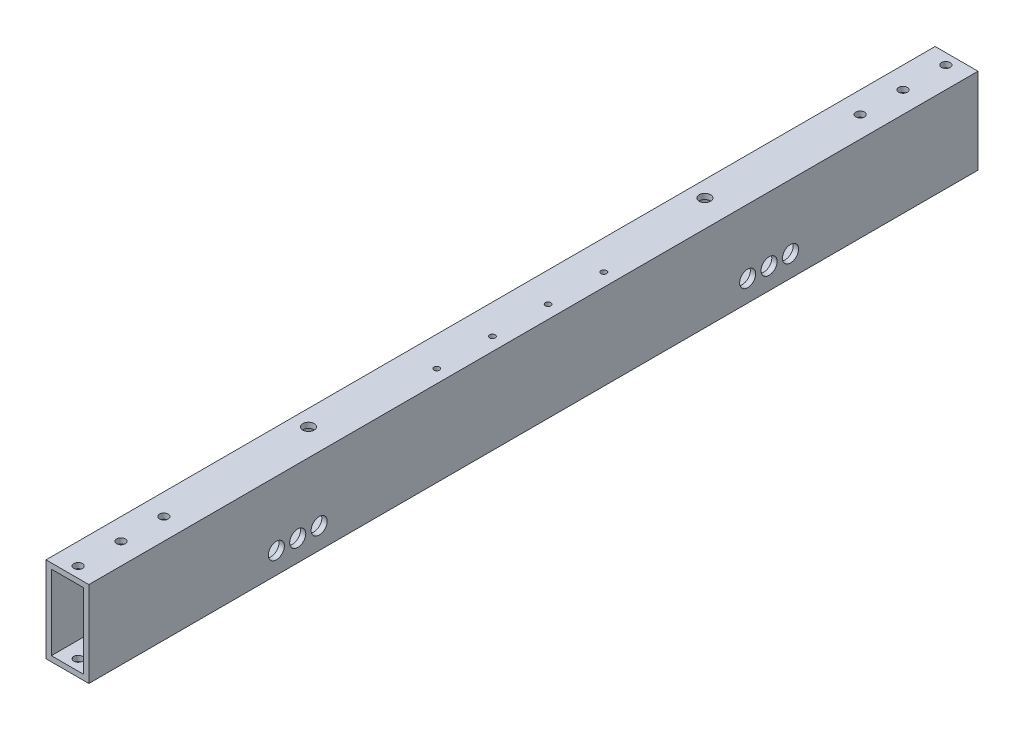
SolidWorks part; units mm, degrees
material "6061-T6 (SS)"
ref_plane "Front" through (0, 0, 0) normal (0, 0, 1) x (1, 0, 0)
ref_plane "Top" through (0, 0, 0) normal (0, 1, 0) x (1, 0, 0)
ref_plane "Right" through (0, 0, 0) normal (1, 0, 0) x (0, 0, -1)
sketch "Sketch1" plane through (0, 0, 0) normal (0, 0, 1) x (1, 0, 0)
  line L1 (-12.7, -25.4) -> (12.7, -25.4)
  line L2 (-12.7, -25.4) -> (-12.7, 25.4)
  line L3 (-12.7, 25.4) -> (12.7, 25.4)
  line L4 (12.7, -25.4) -> (12.7, 25.4)
  line L5 (-12.7, -25.4) -> (12.7, 25.4) construction
  line L6 (-12.7, 25.4) -> (12.7, -25.4) construction
  point P0 (0, 0)
  dimension "D1" = 25.4
  dimension "D2" = 50.8
extrude "Extrude-Thin1" add sketch "Sketch1" along normal blind 527.05 thin thin type one direction reverse wall 3.175
hole_wizard "#10 Clearance Hole1" positions "Sketch2" profile "Sketch3" hole size "#10" standard "ANSI Inch" end condition through all
sketch "Sketch2" plane through (0, 25.4, 0) normal (0, 1, 0) x (1, 0, 0)
  line L0 (12.7, -527.05) -> (-12.7, -527.05) construction
  line L1 (-12.7, -527.05) -> (-12.7, 0) construction
  point P0 (0, -520.7)
  point P2 (0, -495.3)
  point P4 (0, -469.9)
  point P13 (0, -6.35)
  point P15 (0, -31.75)
  point P17 (0, -57.15)
  dimension "D1" = 6.35
  dimension "D2" = 25.4
  dimension "D3" = 25.4
  dimension "D4" = 12.7
  dimension "D5" = 6.35
  dimension "D6" = 25.4
  dimension "D7" = 25.4
sketch "Sketch3" plane through (0, 25.4, 520.7) normal (1, 0, 0) x (0, 0, 1)
  line L0 (0, 0) -> (0, 50.8)
  line L1 (0, 50.8) -> (2.5527, 50.8)
  line L2 (2.5527, 50.8) -> (2.5527, 0)
  line L5 (2.5527, 0) -> (0, 0)
  line L11 (0, -6.35) -> (0, 107.95) construction
  dimension "Thru Hole Dia." = 5.1054
  dimension "Thru Hole Depth" = 50.8
sketch "Sketch8" plane through (0, -25.4, 0) normal (0, -1, 0) x (-1, 0, 0)
  point P0 (3.175, -451.358)
  point P3 (-3.175, -425.958)
  point P6 (3.175, -400.558)
  point P9 (-3.175, -375.158)
  point P12 (3.175, -349.758)
  point P19 (3.175, -298.958)
  point P26 (3.175, -248.158)
  point P29 (-3.175, -222.758)
  point P32 (3.175, -197.358)
  point P35 (-3.175, -171.958)
  point P38 (3.175, -146.558)
  point P41 (-3.175, -121.158)
  point P48 (-3.175, -70.358)
  point P55 (-3.175, -324.358)
  point P58 (-3.175, -273.558)
  point P61 (3.175, -95.758)
hole_wizard "1/8 (0.13) Diameter Hole1" positions "Sketch8" profile "Sketch7" hole size "1/8" standard "ANSI Inch" end condition up to next
sketch "Sketch7" plane through (-3.175, -25.4, 451.358) normal (1, 0, 0) x (0, 0, -1)
  line L0 (0, 0) -> (0, 3.175)
  line L1 (0, 3.175) -> (1.651, 3.175)
  line L2 (1.651, 3.175) -> (1.651, 0)
  line L5 (1.651, 0) -> (0, 0)
  line L11 (0, -6.35) -> (0, 107.95) construction
  dimension "Thru Hole Dia." = 3.302
  dimension "Thru Hole Depth" = 3.175
sketch "Sketch11" plane through (0, 25.4, 0) normal (0, 1, 0) x (1, 0, 0)
  point P0 (4.9213, -313.055)
  point P3 (4.9213, -280.035)
  point P6 (4.9213, -247.015)
  point P9 (4.9213, -213.995)
hole_wizard "1/8 (0.13) Diameter Hole2" positions "Sketch11" profile "Sketch10" hole size "1/8" standard "ANSI Inch" end condition up to next
sketch "Sketch10" plane through (4.9213, 25.4, 313.055) normal (1, 0, 0) x (0, 0, 1)
  line L0 (0, 0) -> (0, 3.175)
  line L1 (0, 3.175) -> (1.651, 3.175)
  line L2 (1.651, 3.175) -> (1.651, 0)
  line L5 (1.651, 0) -> (0, 0)
  line L11 (0, -6.35) -> (0, 107.95) construction
  dimension "Thru Hole Dia." = 3.302
  dimension "Thru Hole Depth" = 3.175
sketch "Sketch14" plane through (0, 25.4, 0) normal (0, 1, 0) x (1, 0, 0)
  line L0 (12.7, 0) -> (-12.7, 0) construction
  line L1 (12.7, -527.05) -> (-12.7, -527.05) construction
  line L2 (-12.7, -527.05) -> (-12.7, 0) construction
  point P0 (-3.175, -146.05)
  point P2 (-3.175, -381)
  dimension "D1" = 146.05
  dimension "D2" = 146.05
  dimension "D3" = 9.525
hole_wizard "1/4 Clearance Hole1" positions "Sketch14" profile "Sketch13" hole size "1/4" standard "ANSI Inch"
sketch "Sketch13" plane through (-3.175, 25.4, 146.05) normal (1, 0, 0) x (0, 0, 1)
  line L0 (0, 0) -> (0, 12.7486)
  line L1 (0, 12.7486) -> (3.3782, 10.7188)
  line L2 (3.3782, 10.7188) -> (3.3782, 0)
  line L5 (3.3782, 0) -> (0, 0)
  line L10 (0, 12.7486) -> (-3.3782, 10.7188) construction
  line L11 (0, -6.35) -> (0, 107.95) construction
  dimension "Hole Dia." = 6.7564
  dimension "Hole Depth" = 10.7188
  dimension "Drill Angle" = 118
sketch "Sketch17" plane through (12.7, 0, 0) normal (1, 0, 0) x (0, 0, -1)
  point P38 (-111.125, -12.7)
  point P41 (-123.825, -12.7)
  point P44 (-136.525, -12.7)
  point P48 (-390.525, -12.7)
  point P51 (-415.925, -12.7)
  point P54 (-403.225, -12.7)
hole_wizard "CBORE for #10 Socket Head Cap Screw1" positions "Sketch17" profile "Sketch16" counterbore size "#10" standard "ANSI Inch" end condition through all
sketch "Sketch16" plane through (12.7, -12.7, 111.125) normal (0, 1, 0) x (0, 0, -1)
  line L0 (0, 0) -> (0, 25.4)
  line L1 (0, 25.4) -> (2.5527, 25.4)
  line L3 (2.5527, 25.4) -> (2.5527, 8.001)
  line L4 (2.5527, 8.001) -> (4.7625, 8.001)
  line L5 (4.7625, 8.001) -> (4.7625, 0)
  line L7 (4.7625, 0) -> (0, 0)
  line L11 (0, -6.35) -> (0, 107.95) construction
  dimension "Thru Hole Dia." = 5.1054
  dimension "Thru Hole Depth" = 25.4
  dimension "C'Bore Dia." = 9.525
  dimension "C'Bore Depth" = 8.001
